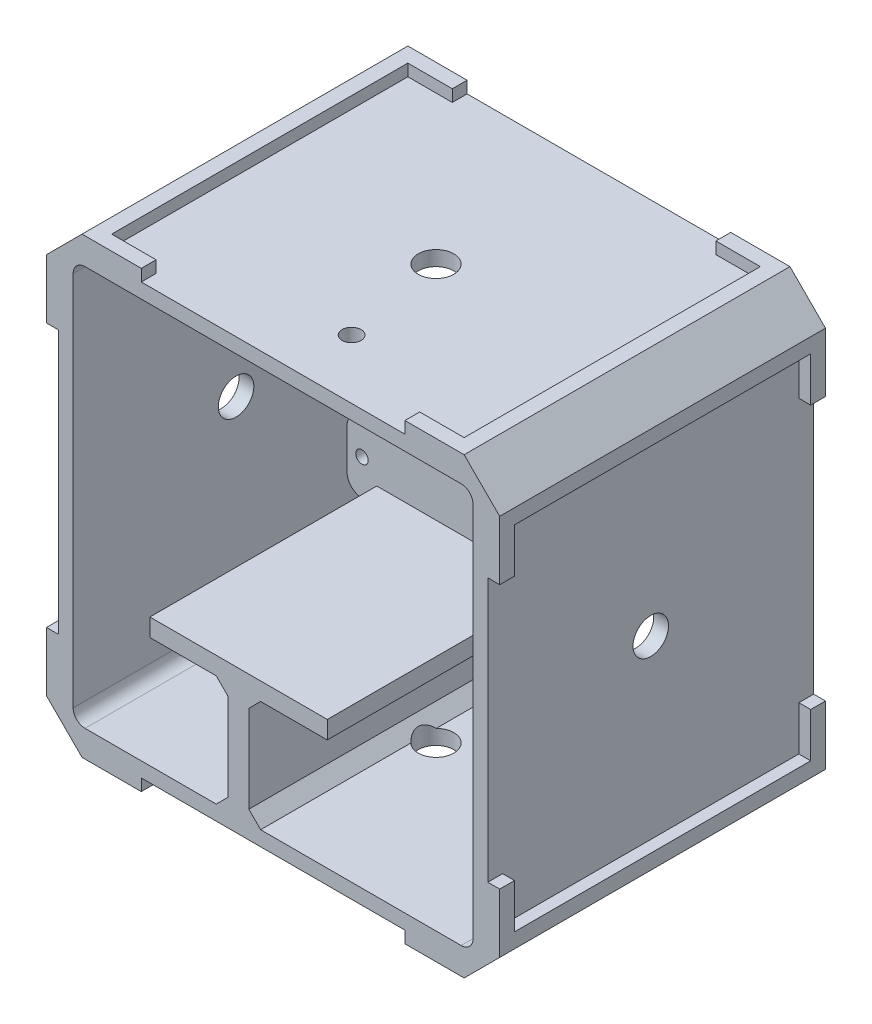
SolidWorks part; units mm, degrees
ref_plane "Front Plane" through (0, 0, 0) normal (0, 0, 1) x (1, 0, 0)
ref_plane "Top Plane" through (0, 0, 0) normal (0, 1, 0) x (1, 0, 0)
ref_plane "Right Plane" through (0, 0, 0) normal (1, 0, 0) x (0, 0, -1)
sketch "Sketch1" plane through (0, 0, 0) normal (0, 0, 1) x (1, 0, 0)
  line L0 (-33.75, -33.75) -> (33.75, -33.75) construction
  line L1 (-31.75, 33.75) -> (31.75, 33.75)
  line L2 (-33.75, 31.75) -> (-33.75, -31.75)
  line L3 (-31.75, -33.75) -> (31.75, -33.75)
  line L4 (33.75, 31.75) -> (33.75, -31.75)
  line L5 (-36.25, 32.25) -> (-36.25, -32.25)
  line L6 (33.75, 33.75) -> (33.75, -33.75) construction
  line L7 (-32.25, -36.25) -> (32.25, -36.25)
  line L8 (36.25, 32.25) -> (36.25, -32.25)
  line L9 (-32.25, 36.25) -> (32.25, 36.25)
  line L10 (-36.25, 36.25) -> (-36.25, -36.25) construction
  line L11 (-36.25, 36.25) -> (36.25, 36.25) construction
  line L12 (-33.75, 33.75) -> (33.75, 33.75) construction
  line L13 (-33.75, 33.75) -> (-33.75, -33.75) construction
  line L14 (-36.25, -36.25) -> (36.25, -36.25) construction
  line L15 (36.25, 36.25) -> (36.25, -36.25) construction
  line L16 (55, 0) -> (-55, 0) construction
  line L17 (0, -55) -> (0, 55) construction
  arc A0 (-36.25, 32.25) -> (-32.25, 36.25) centre (-32.25, 32.25) cw
  arc A1 (-31.75, 33.75) -> (-33.75, 31.75) centre (-31.75, 31.75) ccw
  arc A2 (-33.75, -31.75) -> (-31.75, -33.75) centre (-31.75, -31.75) ccw
  arc A3 (31.75, -33.75) -> (33.75, -31.75) centre (31.75, -31.75) ccw
  arc A4 (31.75, 33.75) -> (33.75, 31.75) centre (31.75, 31.75) cw
  arc A5 (-36.25, -32.25) -> (-32.25, -36.25) centre (-32.25, -32.25) ccw
  arc A6 (32.25, -36.25) -> (36.25, -32.25) centre (32.25, -32.25) ccw
  arc A7 (36.25, 32.25) -> (32.25, 36.25) centre (32.25, 32.25) ccw
  point P36 (-33.75, 0)
  point P39 (0, 33.75)
  dimension "D3" = 4
  dimension "D4" = 2
  dimension "D5" = 2
  dimension "D6" = 4
  dimension "D1" = 67.5
  dimension "D2" = 2.5
extrude "Boss-Extrude1" add sketch "Sketch1" along normal blind 55
sketch "Sketch2" plane through (0, 0, 0) normal (0, 0, 1) x (1, 0, 0)
  line L1 (-33.75, 33.75) -> (33.75, 33.75)
  line L2 (-33.75, 33.75) -> (-33.75, -33.75)
  line L3 (-33.75, -33.75) -> (33.75, -33.75)
  line L4 (33.75, 33.75) -> (33.75, -33.75)
extrude "Boss-Extrude2" add sketch "Sketch2" along normal blind 2.5
sketch "Sketch4" plane through (0, 0, 0) normal (0, 0, -1) x (-1, 0, 0)
  line L0 (-32.25, 36.25) -> (32.25, 36.25) construction
  line L1 (-36.25, -32.25) -> (-36.25, 32.25) construction
  circle A0 centre (-28.75, 28.75) radius 1.65
  dimension "D3" = 3.3
  dimension "D1" = 7.5
  dimension "D2" = 7.5
extrude "Cut-Extrude2" cut sketch "Sketch4" against normal up to next
mirror "Mirror1" about plane through (0, 0, 0) normal (1, 0, 0) of "Cut-Extrude2"
mirror "Mirror2" about plane through (0, 0, 0) normal (0, 1, 0) of "Mirror1"
sketch "Sketch5" plane through (0, 0, 0) normal (1, 0, 0) x (0, 0, -1)
  line L2 (-16.7, 12) -> (-16.7, -12)
  line L3 (-16.7, -12) -> (-60.4, -12)
  line L6 (-13.7, -15) -> (-63.4, -15)
  line L7 (-13.7, 12) -> (-13.7, -15)
  line L9 (-60.4, -12) -> (-63.4, -12)
  line L10 (-63.4, -12) -> (-63.4, -15)
  line L11 (-60.4, 12) -> (-60.4, -12) construction
  line L12 (-63.4, 15) -> (-63.4, -15) construction
  line L13 (0, 39.875) -> (0, -39.875) construction
  line L15 (-16.7, 12) -> (-13.7, 12)
  line L16 (-13.7, 15) -> (-13.7, -15) construction
  line L17 (-13.7, 15) -> (-63.4, 15) construction
  line L18 (-16.7, 12) -> (-60.4, 12) construction
  point P4 (0, 0)
  point P11 (0, 0)
  point P12 (0, 0)
  point P13 (0, 0)
  point P14 (0, 0)
  dimension "D1" = 24
  dimension "D2" = 49.7
  dimension "D4" = 13.7
  dimension "D3" = 3
extrude "Boss-Extrude3" add sketch "Sketch5" along normal blind 14.6 and the other way blind 25.8 separate body
sketch "Sketch6" plane through (0, 0, 63.4) normal (0, 0, 1) x (1, 0, 0)
  line L1 (-25.8, -12) -> (12.1, -12)
  line L2 (-25.8, -12) -> (-25.8, -15)
  line L3 (-25.8, -15) -> (-7.6, -15)
  line L4 (12.1, -12) -> (12.1, -15)
  line L6 (-25.8, -36.25) -> (12.1, -36.25)
  line L7 (-25.8, -36.25) -> (-25.8, -33.75)
  line L8 (-25.8, -33.75) -> (-7.6, -33.75)
  line L9 (12.1, -36.25) -> (12.1, -33.75)
  line L10 (-4.1, -15) -> (12.1, -15)
  line L12 (-7.6, -15) -> (-7.6, -33.75)
  line L14 (-4.1, -15) -> (-4.1, -33.75)
  line L15 (-4.1, -33.75) -> (12.1, -33.75)
  line L16 (-25.8, -12) -> (-25.8, -15) construction
  line L17 (-32.25, -36.25) -> (32.25, -36.25) construction
  point P4 (-25.8, -12)
  point P5 (-7.6, -14.5)
  point P10 (-25.8, -36.25)
  point P16 (0, 0)
  point P17 (-25.8, -33.75)
  dimension "D1" = 3
  dimension "D2" = 2.5
  dimension "D3" = 37.9
  dimension "D4" = 37.9
  dimension "D5" = 3.5
  dimension "D6" = 18.2
  dimension "D7" = 18.2
extrude "Boss-Extrude4" add sketch "Sketch6" against normal up to vertex (49.7 mm away) up to point (14.6, 12, 13.7)
sketch "Sketch7" plane through (0, 0, 63.4) normal (0, 0, 1) x (1, 0, 0)
  line L0 (-25.8, -12) -> (-25.8, -15) construction
  line L1 (-25.8, -13.5) -> (12.1, -13.5)
  line L2 (-25.8, -13.5) -> (-25.8, -36.25)
  line L3 (-25.8, -36.25) -> (12.1, -36.25)
  line L4 (12.1, -13.5) -> (12.1, -36.25)
  line L7 (12.1, -36.25) -> (12.1, -33.75) construction
  point P6 (12.1, -36.25)
  point P8 (12.1, -33.75)
  point P10 (0, 0)
  point P11 (0, 0)
  point P12 (0, 0)
extrude "Cut-Extrude3" cut sketch "Sketch7" against normal blind 8.4
ref_plane "Plane1" through (-11.1, 0, 0) normal (-1, 0, 0) x (0, 0, 1)
sketch "Sketch10" [suppressed] plane through (-36.25, 0, 0) normal (-1, 0, 0) x (0, 0, 1)
  circle A0 centre (22.3967, 9) radius 1.5
  circle A1 centre (22.3967, -9) radius 1.5
  dimension "D1" = 3
  dimension "D2" = 3
extrude "Cut-Extrude4" [suppressed] cut sketch "Sketch10" against normal through all
sketch "Sketch12" plane through (0, 36.25, 0) normal (0, 1, 0) x (1, 0, 0)
  line L0 (-32.25, -55) -> (-32.25, 0) construction
  line L1 (32.25, -55) -> (29.75, -55)
  line L2 (32.25, -55) -> (32.25, -45)
  line L3 (32.25, -45) -> (29.75, -45)
  line L4 (29.75, -52.5) -> (29.75, -45)
  line L5 (32.25, -55) -> (22.25, -55)
  line L6 (32.25, -55) -> (32.25, -52.5)
  line L7 (29.75, -52.5) -> (22.25, -52.5)
  line L8 (22.25, -55) -> (22.25, -52.5)
  line L10 (-32.25, 0) -> (-32.25, -10)
  line L11 (-32.25, -10) -> (-29.75, -10)
  line L12 (-29.75, -2.5) -> (-29.75, -10)
  line L13 (-32.25, 0) -> (-22.25, 0)
  line L15 (-29.75, -2.5) -> (-22.25, -2.5)
  line L16 (-22.25, 0) -> (-22.25, -2.5)
  line M6 (-32.25, -55) -> (32.25, -55)
  line M7 (32.25, -55) -> (32.25, 0)
  dimension "D1" = 2.5
  dimension "D2" = 10
  dimension "D3" = 2.5
  dimension "D4" = 10
  dimension "D5" = 2.5
extrude "Boss-Extrude7" add sketch "Sketch12" along normal blind 2 contours L8 L2 L3 L4 L7 M6 M7 | L10 L11 L12 L15 L16 L13 region at (31, 36.25, 54.8586)
sketch "Sketch13" plane through (0, 0, 0) normal (0, 0, -1) x (-1, 0, 0)
  line L3 (-33.75, 21.25) -> (-25.25, 21.25)
  line L4 (-21.25, 33.75) -> (-21.25, 25.25)
  line L6 (0, 34.87) -> (0, -34.87) construction
  line L8 (21.25, 33.75) -> (21.25, 25.25)
  line L9 (33.75, 21.25) -> (25.25, 21.25)
  line L12 (34.87, 0) -> (-34.87, 0) construction
  line L17 (33.75, -21.25) -> (25.25, -21.25)
  line L18 (21.25, -33.75) -> (21.25, -25.25)
  line L19 (-21.25, -33.75) -> (-21.25, -25.25)
  line L20 (-33.75, -21.25) -> (-25.25, -21.25)
  line L27 (-33.75, 21.25) -> (-33.75, -21.25)
  line L29 (33.75, 21.25) -> (33.75, -21.25)
  line L34 (-21.25, 33.75) -> (21.25, 33.75)
  line L36 (-21.25, -33.75) -> (21.25, -33.75)
  arc A2 (-25.25, 21.25) -> (-21.25, 25.25) centre (-25.25, 25.25) ccw
  arc A4 (25.25, 21.25) -> (21.25, 25.25) centre (25.25, 25.25) cw
  arc A7 (25.25, -21.25) -> (21.25, -25.25) centre (25.25, -25.25) ccw
  arc A8 (-25.25, -21.25) -> (-21.25, -25.25) centre (-25.25, -25.25) cw
  dimension "D3" = 4
extrude "Cut-Extrude6" cut sketch "Sketch13" against normal up to next and the other way through all
sketch "Sketch15" plane through (0, 36.25, 0) normal (0, 1, 0) x (1, 0, 0)
  line L0 (22.25, -55) -> (-32.25, -55) construction
  line L1 (33.75, -55) -> (33.75, -2.5) construction
  circle A0 centre (3.25, -45) radius 1.6
  dimension "D1" = 3.2
  dimension "D2" = 10
  dimension "D3" = 30.5
extrude "Cut-Extrude8" cut sketch "Sketch15" against normal up to surface (2.5 mm away) and the other way through all up to face at (0, 33.75, 15)
sketch "Sketch16" plane through (-33.75, 0, 0) normal (1, 0, 0) x (0, 0, -1)
  line L0 (-55, 36.25) -> (-10, 36.25) construction
  line L2 (-16, 28.7) -> (-16, 30.35)
  line L7 (-16, 30.35) -> (-8.5, 30.35)
  line L9 (-16, 28.7) -> (-8.5, 28.7)
  line L10 (-8.5, 30.35) -> (-8.5, 28.7)
  line L12 (0, -32.25) -> (0, 32.25) construction
  dimension "D1" = 7.5
  dimension "D2" = 7.55
  dimension "D3" = 16
  dimension "D4" = 1.65
extrude "Boss-Extrude8" add sketch "Sketch16" along normal blind 7
sketch "Sketch17" plane through (0, 0, 13.7) normal (0, 0, -1) x (-1, 0, 0)
  line L0 (-14.6, -15) -> (-14.6, 12) construction
  line L2 (25.8, -15) -> (25.8, 12) construction
  line L3 (25.8, 12) -> (-14.6, 12) construction
  circle A0 centre (-12.1, 9) radius 1.05
  circle A1 centre (-12.1, -9) radius 1.05
  circle A2 centre (23.3, -9) radius 1.05
  dimension "D1" = 2.1
  dimension "D2" = 2.5
  dimension "D3" = 3
  dimension "D4" = 2.5
  dimension "D6" = 18
extrude "Cut-Extrude9" cut sketch "Sketch17" against normal up to next
sketch "Sketch19" plane through (0, 36.25, 0) normal (0, 1, 0) x (1, 0, 0)
  line L0 (32.25, -55) -> (-32.25, 0) construction
  line L1 (-32.25, 0) -> (-22.25, 0) construction
  line L2 (32.25, 0) -> (-32.25, -55) construction
  line L3 (32.25, -45) -> (32.25, 0) construction
  line L4 (32.25, 0) -> (-22.25, 0) construction
  line L5 (-32.25, 0) -> (-32.25, -10) construction
  line L6 (-32.25, 0) -> (-32.25, -10) construction
  circle A0 centre (0, -27.5) radius 3
  dimension "D1" = 6
extrude "Cut-Extrude10" cut sketch "Sketch19" against normal blind 2.5
sketch "Sketch20" plane through (36.25, 0, -36.25) normal (-1, 0, 0) x (0, 0, 1)
  line L0 (36.25, -32.25) -> (36.25, 32.25) construction
  line L1 (36.25, -32.25) -> (36.25, -22.25)
  line L2 (36.25, -32.25) -> (46.25, -32.25)
  line L3 (46.25, -32.25) -> (46.25, -29.75)
  line L4 (38.75, -29.75) -> (46.25, -29.75)
  line L5 (36.25, -32.25) -> (36.25, -22.25)
  line L7 (38.75, -29.75) -> (38.75, -22.25)
  line L8 (36.25, -22.25) -> (38.75, -22.25)
  line L10 (91.25, 32.25) -> (81.25, 32.25)
  line L11 (81.25, 32.25) -> (81.25, 29.75)
  line L12 (88.75, 29.75) -> (81.25, 29.75)
  line L13 (91.25, 32.25) -> (91.25, 22.25)
  line L15 (88.75, 29.75) -> (88.75, 22.25)
  line L16 (91.25, 22.25) -> (88.75, 22.25)
  line M25 (36.25, -32.25) -> (36.25, 32.25)
  line M26 (36.25, 32.25) -> (91.25, 32.25)
  line M27 (91.25, 32.25) -> (91.25, -32.25)
  line M28 (91.25, -32.25) -> (36.25, -32.25)
  dimension "D1" = 2.5
  dimension "D2" = 10
  dimension "D3" = 2.5
  dimension "D4" = 10
  dimension "D5" = 2.5
  dimension "D6" = 55
  dimension "D7" = 64.5
  dimension "D8" = 10
  dimension "D9" = 7.5
  dimension "D10" = 7.5
extrude "Boss-Extrude9" add sketch "Sketch20" against normal blind 2 contours L16 L15 L12 L11 M27 M26 | L8 L7 L4 L3 M25 M28 region at (36.25, -27.25, 0.1414) region at (36.25, 32.1086, 50)
ref_axis "Axis1" through (0, 0, 67.62) along (0, 0, -1)
pattern_circular "CirPattern1" count 4 every 90 about axis through (0, 0, 67.62) along (0, 0, -1) of "Boss-Extrude7", "Cut-Extrude10"
pattern_circular "CirPattern2" count 4 every 90 about axis through (0, 0, 67.62) along (0, 0, -1) of "Boss-Extrude9"
sketch "Sketch22" plane through (0, 0, 55) normal (0, 0, 1) x (1, 0, 0)
  line L0 (-38.25, 32.25) -> (-32.25, 38.25)
  line L1 (-32.25, 38.25) -> (-29.75, 38.25)
  line L8 (-29.75, 38.25) -> (-29.75, 33.75)
  line L13 (-38.25, 29.75) -> (-33.75, 29.75)
  line L20 (-38.25, 29.75) -> (-38.25, 32.25)
  line L24 (-32.25, 38.25) -> (-22.25, 38.25) construction
  line L26 (-33.75, 31.75) -> (-33.75, -31.75) construction
  line L27 (-38.25, 22.25) -> (-38.25, 32.25) construction
  line L28 (0, -34.87) -> (0, 34.87) construction
  line L29 (33.75, 33.75) -> (33.75, 29.75)
  line L30 (33.75, 33.75) -> (29.75, 33.75)
  line L31 (38.25, 29.75) -> (38.25, 32.25)
  line L32 (38.25, 29.75) -> (33.75, 29.75)
  line L33 (-33.75, 33.75) -> (-29.75, 33.75)
  line L34 (-33.75, 33.75) -> (-33.75, 29.75)
  line L37 (29.75, 38.25) -> (29.75, 33.75)
  line L38 (32.25, 38.25) -> (29.75, 38.25)
  line L39 (38.25, 32.25) -> (32.25, 38.25)
  line L40 (34.87, 0) -> (-34.87, 0) construction
  line L41 (38.25, -32.25) -> (32.25, -38.25)
  line L42 (32.25, -38.25) -> (29.75, -38.25)
  line L43 (29.75, -38.25) -> (29.75, -33.75)
  line L44 (-33.75, -33.75) -> (-33.75, -29.75)
  line L45 (-33.75, -33.75) -> (-29.75, -33.75)
  line L46 (38.25, -29.75) -> (33.75, -29.75)
  line L47 (38.25, -29.75) -> (38.25, -32.25)
  line L48 (33.75, -33.75) -> (29.75, -33.75)
  line L49 (33.75, -33.75) -> (33.75, -29.75)
  line L50 (-38.25, -29.75) -> (-38.25, -32.25)
  line L51 (-38.25, -29.75) -> (-33.75, -29.75)
  line L52 (-29.75, -38.25) -> (-29.75, -33.75)
  line L53 (-32.25, -38.25) -> (-29.75, -38.25)
  line L54 (-38.25, -32.25) -> (-32.25, -38.25)
  dimension "D1" = 2.5
  dimension "D2" = 2.5
extrude "Boss-Extrude12" add sketch "Sketch22" against normal through all
sketch "Sketch23" plane through (0, 0, 13.7) normal (0, 0, -1) x (-1, 0, 0)
  line L0 (25.8, 12) -> (-14.6, 12) construction
  line L1 (19.3, 12) -> (25.8, 12)
  line L2 (19.3, 12) -> (19.3, -4)
  line L3 (19.3, -4) -> (25.8, -4)
  line L4 (25.8, 12) -> (25.8, -4)
  line L5 (25.8, -15) -> (25.8, 12) construction
  circle A0 centre (23.3, -9) radius 1.05 construction
  dimension "D1" = 5
  dimension "D2" = 6.5
extrude "Cut-Extrude12" cut sketch "Sketch23" against normal up to next
fillet "Fillet2" radius 1.5 1 edges at (14.6, 12, 15.2)
chamfer "Chamfer1" distance 0.75 angle 45 3 edges at (-26.75, 30.35, 12.25) (-30.25, 30.35, 16) (-33.75, 28.7, 12.25)
sketch "Sketch25" plane through (0, -12, 0) normal (0, 1, 0) x (1, 0, 0)
  line L0 (-25.8, -16.7) -> (14.6, -16.7) construction
  line L1 (14.6, -63.4) -> (11.6, -63.4)
  line L2 (14.6, -63.4) -> (14.6, -28.4)
  line L3 (14.6, -28.4) -> (11.6, -28.4)
  line L4 (11.6, -63.4) -> (11.6, -28.4)
  line L5 (-25.8, -63.4) -> (-20.8, -63.4)
  line L6 (-25.8, -63.4) -> (-25.8, -16.7)
  line L7 (-25.8, -16.7) -> (-20.8, -16.7)
  line L8 (-20.8, -63.4) -> (-20.8, -16.7)
  point P10 (-20.8, -16.7)
  dimension "D1" = 3
  dimension "D2" = 35
  dimension "D3" = 5
extrude "Cut-Extrude13" cut sketch "Sketch25" against normal up to next
fillet "Fillet3" radius 1.5 3 edges at (-19.3, 12, 15.2) (-19.3, -4, 15.2) (-25.8, -4, 15.2)
sketch "Sketch26" plane through (11.6, 0, 0) normal (1, 0, 0) x (0, 0, -1)
  line L0 (-55, -22.25) -> (-55, 22.25) construction
  line L1 (-67.544, -8.4561) -> (-55, -8.4561)
  line L2 (-67.544, -8.4561) -> (-67.544, -18.0422)
  line L3 (-67.544, -18.0422) -> (-55, -18.0422)
  line L4 (-55, -8.4561) -> (-55, -18.0422)
extrude "Cut-Extrude14" cut sketch "Sketch26" against normal through all
sketch "Sketch27" plane through (-33.75, 0, 0) normal (1, 0, 0) x (0, 0, -1)
  line L0 (-55, 31.75) -> (-2.5, 31.75) construction
  line L1 (-15.25, 30.35) -> (-8.5, 30.35)
  line L2 (-15.25, 30.35) -> (-15.25, 31.75)
  line L3 (-15.25, 31.75) -> (-8.5, 31.75)
  line L4 (-8.5, 30.35) -> (-8.5, 31.75)
  line L5 (-8.5, 27.95) -> (-8.5, 30.35) construction
extrude "Boss-Extrude14" add sketch "Sketch27" along normal blind 1.25
chamfer "Chamfer2" distance 2 angle 45 4 edges at (-4.1, -33.75, 34.35) (-7.6, -33.75, 34.35) (-7.6, -15, 34.35) (-4.1, -15, 34.35)
sketch "Sketch28" plane through (0, -12, 0) normal (0, 1, 0) x (1, 0, 0)
  line L0 (-20.8, -16.7) -> (14.6, -16.7) construction
  line L1 (9.15, -16.7) -> (16.7741, -16.7)
  line L2 (9.15, -16.7) -> (9.15, -63.0731)
  line L3 (9.15, -63.0731) -> (16.7741, -63.0731)
  line L4 (16.7741, -16.7) -> (16.7741, -63.0731)
  line L5 (33.75, -55) -> (33.75, -2.5) construction
  dimension "D1" = 24.6
extrude "Cut-Extrude15" cut sketch "Sketch28" against normal up to next
fillet "Fillet5" radius 2.5 2 edges at (14.6, -15, 15.2) (-25.8, -15, 15.2)
